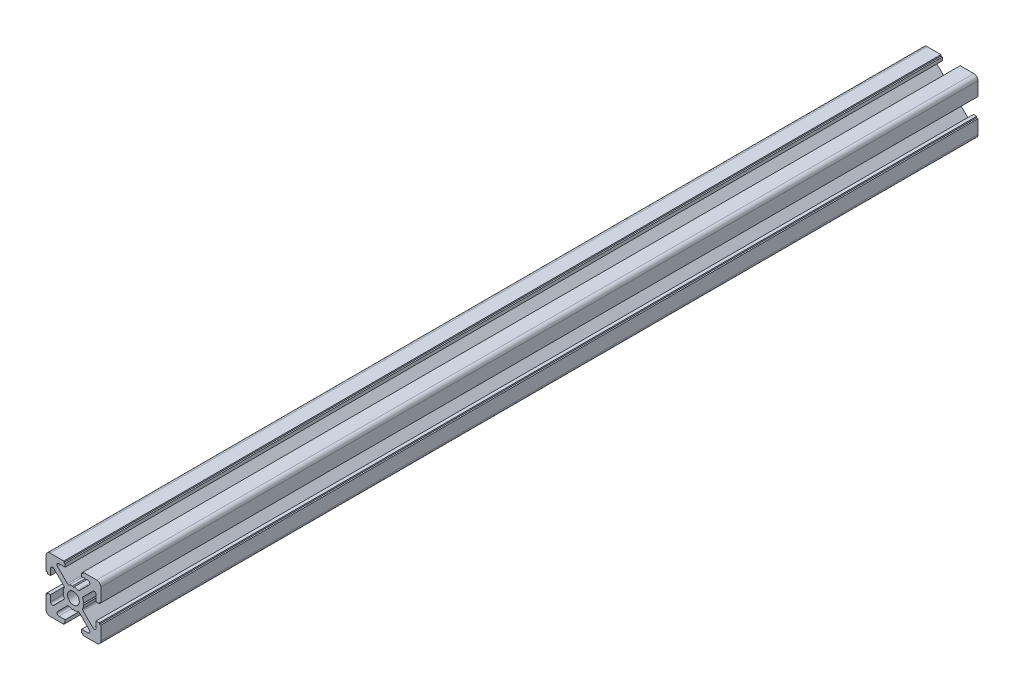
SolidWorks part; units mm, degrees
material "1060 Alloy"
ref_plane "Front Plane" through (0, 0, 0) normal (0, 0, 1) x (1, 0, 0)
ref_plane "Top Plane" through (0, 0, 0) normal (0, 1, 0) x (1, 0, 0)
ref_plane "Right Plane" through (0, 0, 0) normal (1, 0, 0) x (0, 0, -1)
ref_plane "Plane1" through (0, 0, 330) normal (0, 0, 1) x (1, 0, 0)
sketch "Sketch1" plane through (0, 0, 330) normal (0, 0, 1) x (1, 0, 0)
  line L0 (-3.5, -10) -> (-3.5, -9.5)
  line L1 (-3.5, -9.5) -> (-3, -9.5)
  line L2 (-3, -9.5) -> (-3, -8.3)
  line L3 (-3, -8.3) -> (-5.2994, -8.3)
  line L4 (-5.7944, -7.105) -> (-2.1755, -3.4861)
  line L5 (-0.3, -3.738) -> (0, -3.45)
  line L6 (0, -3.45) -> (0.3, -3.738)
  line L7 (2.1755, -3.4861) -> (5.7944, -7.105)
  line L8 (5.2994, -8.3) -> (3, -8.3)
  line L9 (3, -8.3) -> (3, -9.5)
  line L10 (3, -9.5) -> (3.5, -9.5)
  line L11 (3.5, -9.5) -> (3.5, -10)
  line L12 (3.5, -10) -> (8.5, -10)
  line L13 (10, -8.5) -> (10, -3.5)
  line L14 (10, -3.5) -> (9.5, -3.5)
  line L15 (9.5, -3.5) -> (9.5, -3)
  line L16 (9.5, -3) -> (8.3, -3)
  line L17 (8.3, -3) -> (8.3, -5.2994)
  line L18 (7.105, -5.7944) -> (3.4861, -2.1755)
  line L19 (3.738, -0.3) -> (3.45, 0)
  line L20 (3.45, 0) -> (3.738, 0.3)
  line L21 (3.4861, 2.1755) -> (7.105, 5.7944)
  line L22 (8.3, 5.2994) -> (8.3, 3)
  line L23 (8.3, 3) -> (9.5, 3)
  line L24 (9.5, 3) -> (9.5, 3.5)
  line L25 (9.5, 3.5) -> (10, 3.5)
  line L26 (10, 3.5) -> (10, 8.5)
  line L27 (8.5, 10) -> (3.5, 10)
  line L28 (3.5, 10) -> (3.5, 9.5)
  line L29 (3.5, 9.5) -> (3, 9.5)
  line L30 (3, 9.5) -> (3, 8.3)
  line L31 (3, 8.3) -> (5.2994, 8.3)
  line L32 (5.7944, 7.105) -> (2.1755, 3.4861)
  line L33 (0.3, 3.738) -> (0, 3.45)
  line L34 (0, 3.45) -> (-0.3, 3.738)
  line L35 (-2.1755, 3.4861) -> (-5.7944, 7.105)
  line L36 (-5.2994, 8.3) -> (-3, 8.3)
  line L37 (-3, 8.3) -> (-3, 9.5)
  line L38 (-3, 9.5) -> (-3.5, 9.5)
  line L39 (-3.5, 9.5) -> (-3.5, 10)
  line L40 (-3.5, 10) -> (-8.5, 10)
  line L41 (-10, 8.5) -> (-10, 3.5)
  line L42 (-10, 3.5) -> (-9.5, 3.5)
  line L43 (-9.5, 3.5) -> (-9.5, 3)
  line L44 (-9.5, 3) -> (-8.3, 3)
  line L45 (-8.3, 3) -> (-8.3, 5.2994)
  line L46 (-7.105, 5.7944) -> (-3.4861, 2.1755)
  line L47 (-3.738, 0.3) -> (-3.45, 0)
  line L48 (-3.45, 0) -> (-3.738, -0.3)
  line L49 (-3.4861, -2.1755) -> (-7.105, -5.7944)
  line L50 (-8.3, -5.2994) -> (-8.3, -3)
  line L51 (-8.3, -3) -> (-9.5, -3)
  line L52 (-9.5, -3) -> (-9.5, -3.5)
  line L53 (-9.5, -3.5) -> (-10, -3.5)
  line L54 (-10, -3.5) -> (-10, -8.5)
  line L55 (-8.5, -10) -> (-3.5, -10)
  circle A0 centre (0, 0) radius 2.15
  arc A1 (-5.2994, -8.3) -> (-5.7944, -7.105) centre (-5.2994, -7.6) cw
  arc A2 (-2.1755, -3.4861) -> (-1.6076, -3.388) centre (-1.8219, -3.8397) cw
  arc A3 (-1.6076, -3.388) -> (-0.3, -3.738) centre (0, 0) ccw
  arc A4 (0.3, -3.738) -> (1.6076, -3.388) centre (0, 0) ccw
  arc A5 (1.6076, -3.388) -> (2.1755, -3.4861) centre (1.8219, -3.8397) cw
  arc A6 (5.7944, -7.105) -> (5.2994, -8.3) centre (5.2994, -7.6) cw
  arc A7 (8.5, -10) -> (10, -8.5) centre (8.5, -8.5) ccw
  arc A8 (8.3, -5.2994) -> (7.105, -5.7944) centre (7.6, -5.2994) cw
  arc A9 (3.4861, -2.1755) -> (3.388, -1.6076) centre (3.8397, -1.8219) cw
  arc A10 (3.388, -1.6076) -> (3.738, -0.3) centre (0, 0) ccw
  arc A11 (3.738, 0.3) -> (3.388, 1.6076) centre (0, 0) ccw
  arc A12 (3.388, 1.6076) -> (3.4861, 2.1755) centre (3.8397, 1.8219) cw
  arc A13 (7.105, 5.7944) -> (8.3, 5.2994) centre (7.6, 5.2994) cw
  arc A14 (10, 8.5) -> (8.5, 10) centre (8.5, 8.5) ccw
  arc A15 (5.2994, 8.3) -> (5.7944, 7.105) centre (5.2994, 7.6) cw
  arc A16 (2.1755, 3.4861) -> (1.6076, 3.388) centre (1.8219, 3.8397) cw
  arc A17 (1.6076, 3.388) -> (0.3, 3.738) centre (0, 0) ccw
  arc A18 (-0.3, 3.738) -> (-1.6076, 3.388) centre (0, 0) ccw
  arc A19 (-1.6076, 3.388) -> (-2.1755, 3.4861) centre (-1.8219, 3.8397) cw
  arc A20 (-5.7944, 7.105) -> (-5.2994, 8.3) centre (-5.2994, 7.6) cw
  arc A21 (-8.5, 10) -> (-10, 8.5) centre (-8.5, 8.5) ccw
  arc A22 (-8.3, 5.2994) -> (-7.105, 5.7944) centre (-7.6, 5.2994) cw
  arc A23 (-3.4861, 2.1755) -> (-3.388, 1.6076) centre (-3.8397, 1.8219) cw
  arc A24 (-3.388, 1.6076) -> (-3.738, 0.3) centre (0, 0) ccw
  arc A25 (-3.738, -0.3) -> (-3.388, -1.6076) centre (0, 0) ccw
  arc A26 (-3.388, -1.6076) -> (-3.4861, -2.1755) centre (-3.8397, -1.8219) cw
  arc A27 (-7.105, -5.7944) -> (-8.3, -5.2994) centre (-7.6, -5.2994) cw
  arc A28 (-10, -8.5) -> (-8.5, -10) centre (-8.5, -8.5) ccw
extrude "Boss-Extrude1" add sketch "Sketch1" against normal blind 320
sketch "Sketch2" plane through (0, 0, 10) normal (0, 0, -1) x (-1, 0, 0)
  line L0 (-9.5, -3.5) -> (-9.5, -3) construction
  line L1 (-3.4861, 2.1755) -> (-7.105, 5.7944) construction
  line L2 (-8.3, 5.2994) -> (-8.3, 3) construction
  line L3 (-8.3, -3) -> (-8.3, -5.2994) construction
  line L4 (-7.105, -5.7944) -> (-3.4861, -2.1755) construction
  line L5 (-8.3, 3) -> (-9.5, 3) construction
  line L6 (-9.5, -3) -> (-8.3, -3) construction
  line L7 (-3.45, 0) -> (-3.738, 0.3) construction
  line L8 (-3.738, -0.3) -> (-3.45, 0) construction
  line L9 (-10, -3.5) -> (-9.5, -3.5) construction
  line L10 (-9.5, 3) -> (-9.5, 3.5) construction
  line L11 (-9.5, 3.5) -> (-10, 3.5) construction
  line L12 (-9.5, 3) -> (-9.5, 3.5)
  line L13 (-9.5, 3.5) -> (-10, 3.5)
  line L14 (-9.5, -3.5) -> (-9.5, -3)
  line L15 (-10, -3.5) -> (-9.5, -3.5)
  line L16 (-3.738, -0.3) -> (-3.45, 0)
  line L17 (-3.45, 0) -> (-3.738, 0.3)
  line L18 (-9.5, -3) -> (-8.3, -3)
  line L19 (-8.3, 3) -> (-9.5, 3)
  line L20 (-7.105, -5.7944) -> (-3.4861, -2.1755)
  line L21 (-8.3, -3) -> (-8.3, -5.2994)
  line L22 (-8.3, 5.2994) -> (-8.3, 3)
  line L23 (-3.4861, 2.1755) -> (-7.105, 5.7944)
  arc A0 (-7.105, 5.7944) -> (-8.3, 5.2994) centre (-7.6, 5.2994) ccw construction
  arc A1 (-8.3, -5.2994) -> (-7.105, -5.7944) centre (-7.6, -5.2994) ccw construction
  arc A2 (-3.4861, -2.1755) -> (-3.388, -1.6076) centre (-3.8397, -1.8219) ccw construction
  arc A3 (-3.738, -0.3) -> (-3.388, -1.6076) centre (0, 0) ccw construction
  arc A4 (-3.388, 1.6076) -> (-3.738, 0.3) centre (0, 0) ccw construction
  arc A5 (-3.388, 1.6076) -> (-3.4861, 2.1755) centre (-3.8397, 1.8219) ccw construction
  arc A6 (-3.388, 1.6076) -> (-3.4861, 2.1755) centre (-3.8397, 1.8219) ccw
  arc A7 (-3.388, 1.6076) -> (-3.738, 0.3) centre (0, 0) ccw
  arc A8 (-3.738, -0.3) -> (-3.388, -1.6076) centre (0, 0) ccw
  arc A9 (-3.4861, -2.1755) -> (-3.388, -1.6076) centre (-3.8397, -1.8219) ccw
  arc A10 (-8.3, -5.2994) -> (-7.105, -5.7944) centre (-7.6, -5.2994) ccw
  arc A11 (-7.105, 5.7944) -> (-8.3, 5.2994) centre (-7.6, 5.2994) ccw
